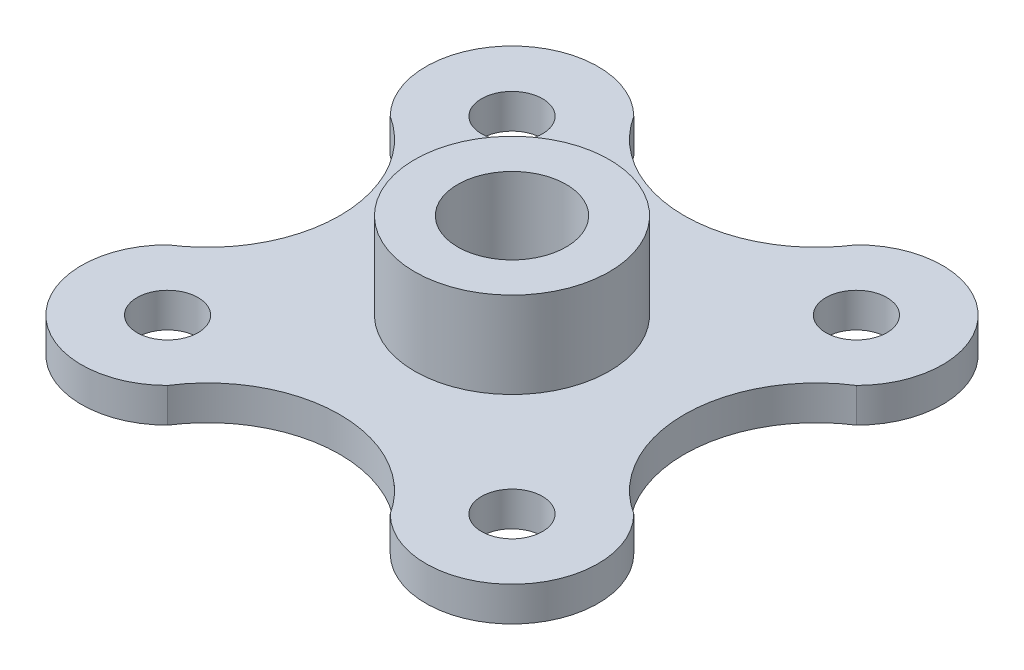
SolidWorks part; units mm, degrees
material "ABS"
ref_plane "Front Plane" through (0, 0, 0) normal (0, 0, 1) x (1, 0, 0)
ref_plane "Top Plane" through (0, 0, 0) normal (0, 1, 0) x (1, 0, 0)
ref_plane "Right Plane" through (0, 0, 0) normal (1, 0, 0) x (0, 0, -1)
sketch "Sketch1" plane through (0, 0, 0) normal (0, 1, 0) x (1, 0, 0)
  line L0 (-17.1901, 8.2099) -> (-8.2099, 17.1901) construction
  line L1 (-12.7, -12.7) -> (12.7, -12.7) construction
  line L2 (-12.7, -12.7) -> (-12.7, 12.7) construction
  line L3 (-12.7, 12.7) -> (12.7, 12.7) construction
  line L4 (12.7, -12.7) -> (12.7, 12.7) construction
  line L5 (-12.7, -12.7) -> (12.7, 12.7) construction
  line L6 (-12.7, 12.7) -> (12.7, -12.7) construction
  line L7 (8.2099, 17.1901) -> (17.1901, 8.2099) construction
  line L8 (-17.1901, -8.2099) -> (-8.2099, -17.1901) construction
  line L9 (8.2099, -17.1901) -> (17.1901, -8.2099) construction
  circle A0 centre (-12.7, 12.7) radius 6.35
  circle A1 centre (12.7, 12.7) radius 6.35
  circle A2 centre (12.7, -12.7) radius 6.35
  circle A3 centre (-12.7, -12.7) radius 6.35
  circle A4 centre (0, 0) radius 7.175
  circle A5 centre (0, 0) radius 4
  arc A6 (-8.2099, 17.1901) -> (8.2099, 17.1901) centre (0, 22.4506) ccw
  arc A7 (-17.1901, 8.2099) -> (-17.1901, -8.2099) centre (-22.4506, 0) cw
  arc A8 (-8.2099, -17.1901) -> (8.2099, -17.1901) centre (0, -22.4506) cw
  arc A9 (17.1901, -8.2099) -> (17.1901, 8.2099) centre (22.4506, 0) cw
  point P0 (0, 0)
  point P16 (-12.7, 12.7)
  point P19 (12.7, 12.7)
  point P22 (-12.7, -12.7)
  point P25 (12.7, -12.7)
  dimension "D1" = 8
  dimension "D2" = 12.7
  dimension "D3" = 3.175
  dimension "D4" = 25.4
extrude "Boss-Extrude1" add sketch "Sketch1" along normal blind 2.54 contours A3 A8 A7 | A2 A9 A1 A6 A0 A7 A3 A8 A4 | A2 A9 A8 | A1 A9 A6 | A4 A5 | A5 | A0 A7 A6 region at (-12.7009, 0, -12.7009) region at (0, 0, -12.2509) region at (12.7009, 0, -12.7009) region at (-12.7009, 0, 12.7009) region at (12.7009, 0, 12.7009) region at (-6.9721, 0, 0) region at (0, 0, 0)
extrude "Boss-Extrude2" add sketch "Sketch1<3>" along normal blind 6.35 from surface contours A4 | A5 starting at face at (0, 2.54, 0)
sketch "Sketch1<3>" plane through (0, 0, 0) normal (0, 1, 0) x (1, 0, 0) same geometry as "Sketch1"
hole_wizard "#8 Clearance Hole1" positions "Sketch3" profile "Sketch4" hole size "#8" standard "ANSI Inch" end condition through all
sketch "Sketch3" plane through (0, 2.54, 0) normal (0, 1, 0) x (1, 0, 0)
  arc A0 (-8.2099, 17.1901) -> (-17.1901, 8.2099) centre (-12.7, 12.7) ccw construction
  arc A1 (17.1901, 8.2099) -> (8.2099, 17.1901) centre (12.7, 12.7) ccw construction
  arc A2 (8.2099, -17.1901) -> (17.1901, -8.2099) centre (12.7, -12.7) ccw construction
  arc A3 (-17.1901, -8.2099) -> (-8.2099, -17.1901) centre (-12.7, -12.7) ccw construction
  point P0 (-12.7, 12.7)
  point P2 (12.7, 12.7)
  point P4 (12.7, -12.7)
  point P6 (-12.7, -12.7)
sketch "Sketch4" plane through (-12.7, 2.54, -12.7) normal (1, 0, 0) x (0, 0, 1)
  line L0 (0, 0) -> (0, 2.54)
  line L1 (0, 2.54) -> (2.2479, 2.54)
  line L2 (2.2479, 2.54) -> (2.2479, 0)
  line L5 (2.2479, 0) -> (0, 0)
  line L11 (0, -6.35) -> (0, 107.95) construction
  dimension "Thru Hole Dia." = 4.4958
  dimension "Thru Hole Depth" = 2.54
